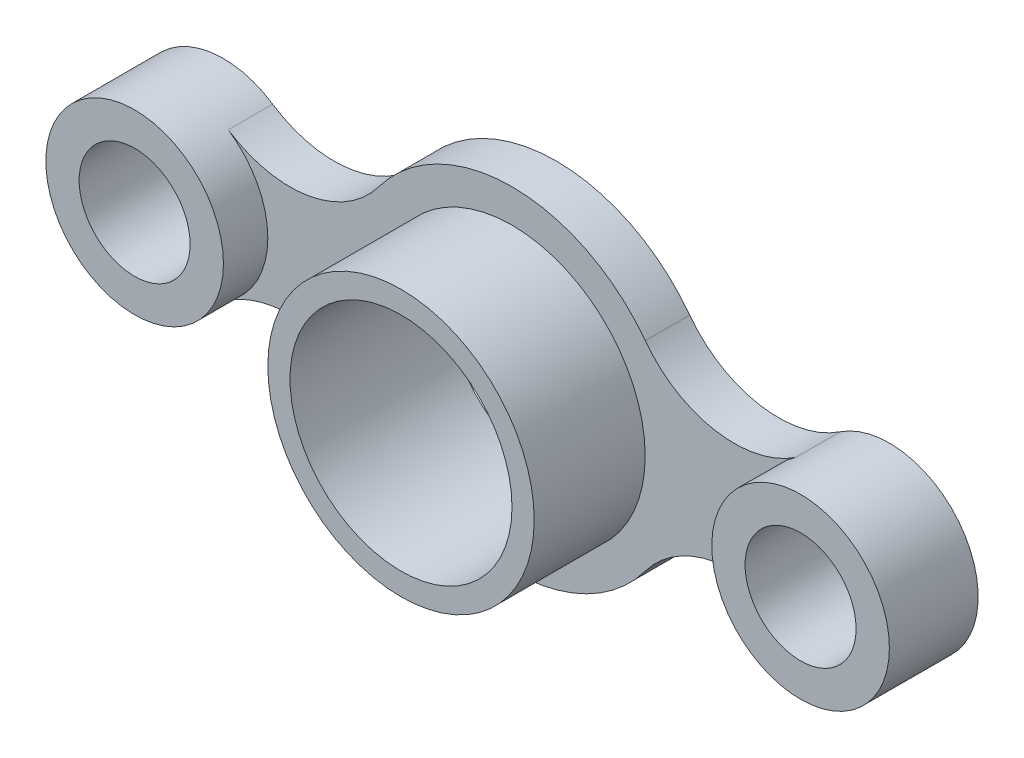
SolidWorks part; units mm, degrees
ref_plane "Front Plane" through (0, 0, 0) normal (0, 0, 1) x (1, 0, 0)
ref_plane "Top Plane" through (0, 0, 0) normal (0, 1, 0) x (1, 0, 0)
ref_plane "Right Plane" through (0, 0, 0) normal (1, 0, 0) x (0, 0, -1)
sketch "Sketch1" plane through (0, 0, 0) normal (0, 0, 1) x (1, 0, 0)
  line L0 (0, 118.8498) -> (0, -152.4967) construction
  line L1 (-172.5764, 0) -> (208.0323, 0) construction
  circle A0 centre (0, 0) radius 50
  circle A1 centre (0, 0) radius 60
  circle A2 centre (0, 0) radius 75
  circle A3 centre (150, 0) radius 25
  circle A4 centre (-150, 0) radius 25
  circle A5 centre (150, 0) radius 40
  circle A6 centre (-150, 0) radius 40
  arc A7 (-127.8148, 33.2839) -> (-60.05, 44.9333) centre (-100.0833, 74.8888) ccw
  arc A8 (127.8148, 33.2839) -> (60.05, 44.9333) centre (100.0833, 74.8888) cw
  arc A9 (127.8148, -33.2839) -> (60.05, -44.9333) centre (100.0833, -74.8888) ccw
  arc A10 (-127.8148, -33.2839) -> (-60.05, -44.9333) centre (-100.0833, -74.8888) cw
  dimension "D1" = 150
  dimension "D2" = 120
  dimension "D3" = 100
  dimension "D4" = 80
  dimension "D5" = 50
  dimension "D6" = 150
  dimension "D7" = 100
extrude "Boss-Extrude4" add sketch "Sketch1" along normal blind 20 contours A6 A10 A2 A7 | A2 A1 | A9 A5 A8 A2 region at (69.1516, -23.0078, 0) region at (91.9815, 0, 0) region at (-91.9815, 0, 0)
extrude "Boss-Extrude5" add sketch "Sketch1<5>" along normal blind 40 contours A6 A4 region at (-115.7313, 18.3419, 0)
sketch "Sketch1<5>" plane through (0, 0, 0) normal (0, 0, 1) x (1, 0, 0) same geometry as "Sketch1"
extrude "Boss-Extrude6" add sketch "Sketch1<6>" along normal blind 40 contours A5 A3 region at (168.3419, 34.2687, 0)
sketch "Sketch1<6>" plane through (0, 0, 0) normal (0, 0, 1) x (1, 0, 0) same geometry as "Sketch1"
extrude "Boss-Extrude7" add sketch "Sketch1<7>" along normal blind 70 contours A1 A0 region at (-58.3029, 0, 0)
sketch "Sketch1<7>" plane through (0, 0, 0) normal (0, 0, 1) x (1, 0, 0) same geometry as "Sketch1"
